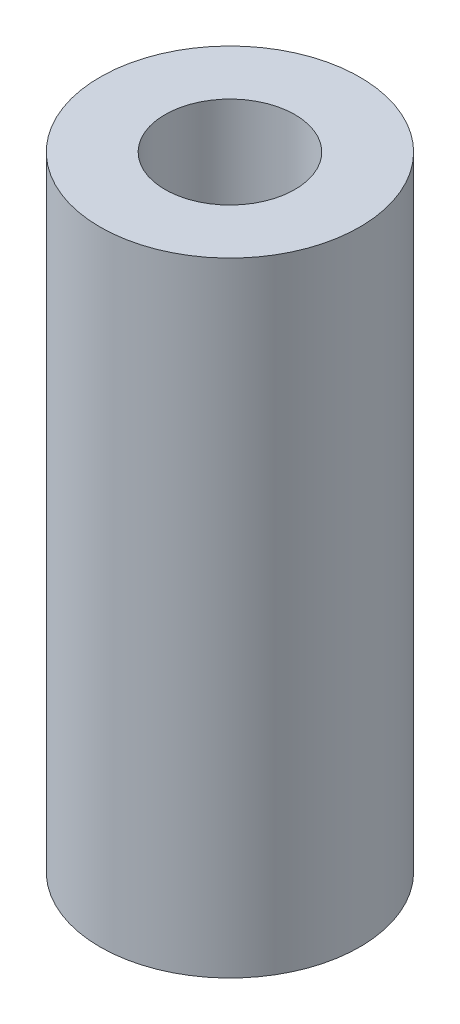
SolidWorks part; units mm, degrees
material "6063-T6"
ref_plane "Front Plane" through (0, 0, 0) normal (0, 0, 1) x (1, 0, 0)
ref_plane "Top Plane" through (0, 0, 0) normal (0, 1, 0) x (1, 0, 0)
ref_plane "Right Plane" through (0, 0, 0) normal (1, 0, 0) x (0, 0, -1)
sketch "Sketch1" plane through (0, 0, 0) normal (0, 1, 0) x (1, 0, 0)
  circle A0 centre (0, 0) radius 2.5
  dimension "D1" = 5
extrude "Boss-Extrude1" add sketch "Sketch1" along normal blind 12
hole_wizard "Tap Drill for M3x0.5 Tap1" positions "Sketch2" profile "Sketch3" hole size "M3x0.5" standard "ANSI Metric" end condition through all
sketch "Sketch2" plane through (0, 0, 0) normal (0, -1, 0) x (-1, 0, 0)
  point P0 (0, 0)
sketch "Sketch3" plane through (0, 0, 0) normal (1, 0, 0) x (0, 0, -1)
  line L0 (0, 0) -> (0, 12)
  line L1 (0, 12) -> (1.25, 12)
  line L2 (1.25, 12) -> (1.25, 0)
  line L5 (1.25, 0) -> (0, 0)
  line L11 (0, -6.35) -> (0, 107.95) construction
  dimension "Thru Hole Dia." = 2.5
  dimension "Thru Hole Depth" = 12
